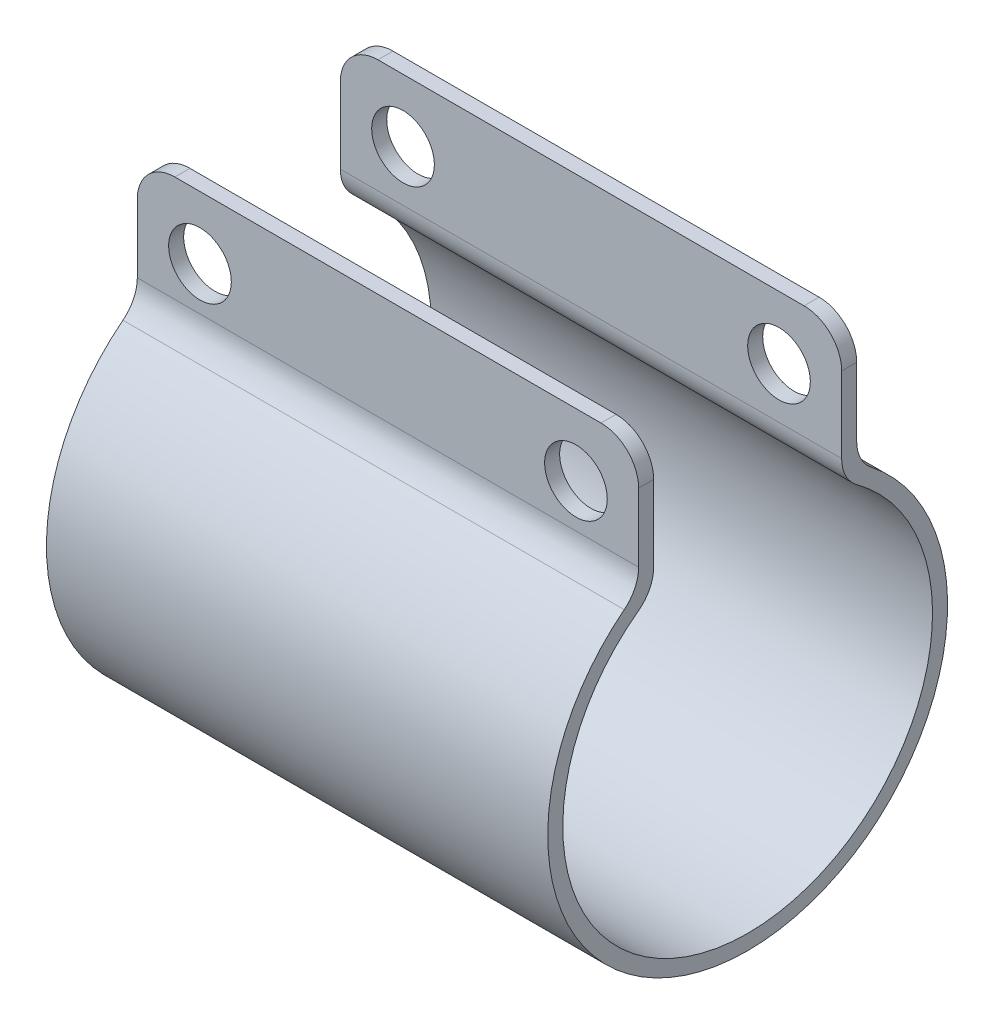
SolidWorks part; units mm, degrees
ref_plane "Front Plane" through (0, 0, 0) normal (0, 0, 1) x (1, 0, 0)
ref_plane "Top Plane" through (0, 0, 0) normal (0, 1, 0) x (1, 0, 0)
ref_plane "Right Plane" through (0, 0, 0) normal (1, 0, 0) x (0, 0, -1)
sketch "Sketch1" plane through (0, 0, 0) normal (1, 0, 0) x (0, 0, -1)
  line L0 (9.525, 16.1301) -> (9.525, 29.6778)
  line L1 (9.525, 29.6778) -> (11.049, 29.6778)
  line L2 (11.049, 29.6778) -> (11.049, 16.9778)
  line L3 (-9.525, 16.1301) -> (-9.525, 29.6778)
  line L4 (-9.525, 29.6778) -> (-11.049, 29.6778)
  line L5 (-11.049, 29.6778) -> (-11.049, 16.9778)
  circle A0 centre (0, 0) radius 17.4625 construction
  arc A1 (-9.525, 16.1301) -> (9.525, 16.1301) centre (0, 0) ccw
  arc A2 (-11.049, 16.9778) -> (11.049, 16.9778) centre (0, 0) ccw
  point P3 (0, 0)
  point P4 (0, 0)
  dimension "D1" = 34.925
  dimension "D2" = 1.27
  dimension "D3" = 1.524
  dimension "D4" = 1.524
  dimension "D5" = 19.05
  dimension "D6" = 12.7
extrude "Boss-Extrude1" add sketch "Sketch1" along normal blind 50.8
sketch "Sketch2" plane through (0, 0, 0) normal (0, 0, 1) x (1, 0, 0)
  line L0 (6.35, 23.3278) -> (44.45, 23.3278) construction
  line L1 (50.8, 29.6778) -> (0, 29.6778) construction
  line L2 (50.8, 29.6778) -> (50.8, 16.9778) construction
  circle A0 centre (6.35, 23.3278) radius 3.175
  circle A1 centre (44.45, 23.3278) radius 3.175
  point P6 (25.4, 29.6778)
  point P7 (25.4, 23.3278)
  point P10 (50.8, 23.3278)
  dimension "D1" = 6.35
  dimension "D2" = 38.1
extrude "Cut-Extrude1" cut sketch "Sketch2" against normal through all and the other way through all
fillet "Fillet1" radius 3.81 8 edges at (25.4, 16.9778, 11.049) (25.4, 16.9778, -11.049) (50.8, 29.6778, 10.287) (50.8, 29.6778, -10.287) (0, 29.6778, -10.287) (0, 29.6778, 10.287) (25.4, 16.1301, 9.525) (25.4, 16.1301, -9.525)
